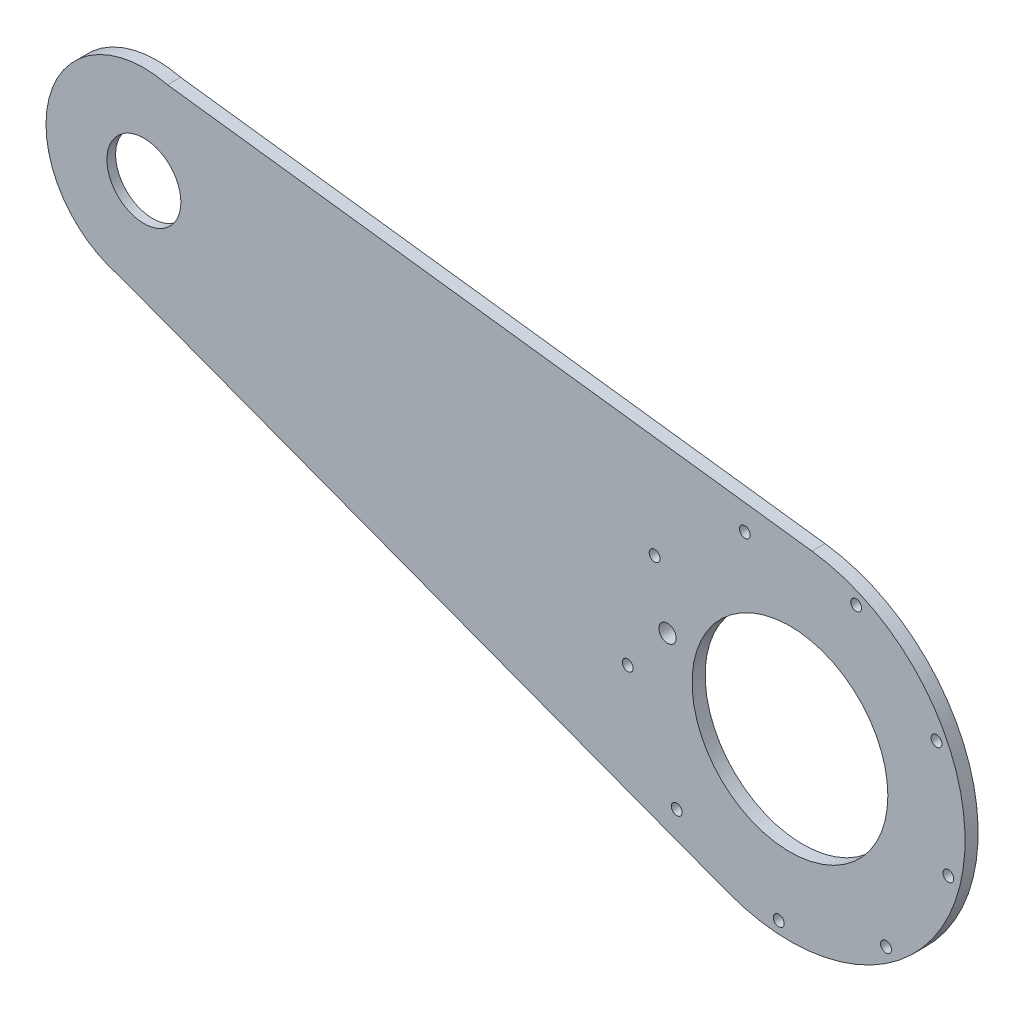
SolidWorks part; units mm, degrees
ref_plane "前视基准面" through (0, 0, 0) normal (0, 0, 1) x (1, 0, 0)
ref_plane "上视基准面" through (0, 0, 0) normal (0, 1, 0) x (1, 0, 0)
ref_plane "右视基准面" through (0, 0, 0) normal (1, 0, 0) x (0, 0, -1)
sketch "草图2" plane through (0, 0, 0) normal (0, 0, 1) x (1, 0, 0)
  line L0 (-94.4003, 60.3379) -> (-122.5464, 67.3235)
  line L1 (-122.5464, 67.3235) -> (-342.1674, 121.8314) construction
  line L2 (-242.8951, 97.1929) -> (-234.6136, 130.5606) construction
  line L3 (-242.8951, 97.1929) -> (-252.9342, 56.7435) construction
  line L4 (-248.3149, 75.3555) -> (-108.6007, 22.6761)
  line L5 (-237.4752, 119.0304) -> (-89.3429, 100.2689)
  arc A6 (-120.6052, 66.8418) -> (-124.4875, 67.8053) centre (-122.5464, 67.3235) ccw
  arc A7 (-124.4875, 67.8053) -> (-120.6052, 66.8418) centre (-122.5464, 67.3235) ccw
  arc A8 (-122.6148, 83.0399) -> (-121.1101, 83.7225) centre (-122.6148, 85.0399) ccw
  arc A9 (-123.8343, 83.4547) -> (-122.6148, 83.0399) centre (-122.6148, 85.0399) ccw
  arc A10 (-123.8343, 83.4547) -> (-125.5111, 84.0251) centre (-125.5111, 81.2751) ccw
  arc A11 (-125.5111, 84.0251) -> (-126.8989, 78.901) centre (-125.5111, 81.2751) ccw
  arc A12 (-126.1212, 76.2764) -> (-126.8989, 78.901) centre (-127.9083, 77.1743) ccw
  arc A13 (-126.1212, 76.2764) -> (-126.7049, 75.0573) centre (-94.4003, 60.3379) ccw
  arc A14 (-129.1382, 73.9829) -> (-126.7049, 75.0573) centre (-128.5249, 75.8865) ccw
  arc A15 (-129.1382, 73.9829) -> (-131.6495, 72.7096) centre (-129.7514, 72.0792) ccw
  arc A16 (-131.6495, 72.7096) -> (-133.1115, 66.8189) centre (-94.4003, 60.3379) ccw
  arc A17 (-133.1115, 66.8189) -> (-131.487, 64.5192) centre (-131.139, 66.4887) ccw
  arc A18 (-129.8385, 62.4317) -> (-131.487, 64.5192) centre (-131.835, 62.5497) ccw
  arc A19 (-129.8385, 62.4317) -> (-129.8925, 61.0828) centre (-94.4003, 60.3379) ccw
  arc A20 (-130.6064, 59.5927) -> (-129.8925, 61.0828) centre (-131.892, 61.1248) ccw
  arc A21 (-131.8073, 59.1266) -> (-130.6064, 59.5927) centre (-131.892, 61.1248) ccw
  arc A22 (-131.8073, 59.1266) -> (-133.4584, 58.4857) centre (-131.6907, 56.3791) ccw
  arc A23 (-133.4584, 58.4857) -> (-131.2278, 53.6683) centre (-131.6907, 56.3791) ccw
  arc A24 (-128.9449, 52.1577) -> (-131.2278, 53.6683) centre (-130.8911, 51.6968) ccw
  arc A25 (-128.9449, 52.1577) -> (-122.0677, 38.0946) centre (-94.4003, 60.3379) ccw
  arc A26 (-121.6568, 36.4942) -> (-122.0677, 38.0946) centre (-123.6264, 36.8415) ccw
  arc A27 (-122.2771, 35.3652) -> (-121.6568, 36.4942) centre (-123.6264, 36.8415) ccw
  arc A28 (-122.2771, 35.3652) -> (-123.1299, 33.813) centre (-120.4217, 33.3354) ccw
  arc A29 (-123.1299, 33.813) -> (-118.3246, 31.5564) centre (-120.4217, 33.3354) ccw
  arc A30 (-115.6049, 31.8666) -> (-118.3246, 31.5564) centre (-116.7995, 30.2626) ccw
  arc A31 (-115.6049, 31.8666) -> (-101.297, 25.5143) centre (-94.4003, 60.3379) ccw
  arc A32 (-99.9535, 24.5524) -> (-101.297, 25.5143) centre (-101.6856, 23.5524) ccw
  arc A33 (-99.703, 23.2889) -> (-99.9535, 24.5524) centre (-101.6856, 23.5524) ccw
  arc A34 (-99.703, 23.2889) -> (-99.3585, 21.5516) centre (-96.977, 22.9266) ccw
  arc A35 (-99.3585, 21.5516) -> (-94.227, 22.9117) centre (-96.977, 22.9266) ccw
  arc A36 (-92.3429, 24.8976) -> (-94.227, 22.9117) centre (-92.227, 22.901) ccw
  arc A37 (-92.3429, 24.8976) -> (-77.2993, 29.2283) centre (-94.4003, 60.3379) ccw
  arc A38 (-75.6518, 29.3551) -> (-77.2993, 29.2283) centre (-76.3358, 27.4757) ccw
  arc A39 (-74.6477, 28.5482) -> (-75.6518, 29.3551) centre (-76.3358, 27.4757) ccw
  arc A40 (-74.6477, 28.5482) -> (-73.2671, 27.4387) centre (-72.3266, 30.0229) ccw
  arc A41 (-73.2671, 27.4387) -> (-70.2105, 31.7792) centre (-72.3266, 30.0229) ccw
  arc A42 (-70.0437, 34.5115) -> (-70.2105, 31.7792) centre (-68.6715, 33.0565) ccw
  arc A43 (-70.0437, 34.5115) -> (-61.3033, 47.4989) centre (-94.4003, 60.3379) ccw
  arc A44 (-60.1227, 48.655) -> (-61.3033, 47.4989) centre (-59.4387, 46.7756) ccw
  arc A45 (-58.8349, 48.6823) -> (-60.1227, 48.655) centre (-59.4387, 46.7756) ccw
  arc A46 (-58.8349, 48.6823) -> (-57.0642, 48.7198) centre (-58.0047, 51.304) ccw
  arc A47 (-57.0642, 48.7198) -> (-57.5126, 54.0096) centre (-58.0047, 51.304) ccw
  arc A48 (-59.1411, 56.2099) -> (-57.5126, 54.0096) centre (-57.1547, 55.9773) ccw
  arc A49 (-59.1411, 56.2099) -> (-58.9003, 60.3379) centre (-94.4003, 60.3379) ccw
  arc A50 (-58.9003, 60.3379) -> (-60.7938, 71.777) centre (-94.4003, 60.3379) ccw
  arc A51 (-60.6325, 73.4215) -> (-60.7938, 71.777) centre (-58.9004, 72.4215) ccw
  arc A52 (-59.6635, 74.2702) -> (-60.6325, 73.4215) centre (-58.9004, 72.4215) ccw
  arc A53 (-59.6635, 74.2702) -> (-58.3312, 75.4371) centre (-60.7127, 76.8121) ccw
  arc A54 (-58.3312, 75.4371) -> (-62.0749, 79.2011) centre (-60.7127, 76.8121) ccw
  arc A55 (-64.7367, 79.8398) -> (-62.0749, 79.2011) centre (-63.0655, 80.9385) ccw
  arc A56 (-64.7367, 79.8398) -> (-76.0091, 90.7026) centre (-94.4003, 60.3379) ccw
  arc A57 (-76.9426, 92.066) -> (-76.0091, 90.7026) centre (-74.973, 92.4133) ccw
  arc A58 (-76.7458, 93.339) -> (-76.9426, 92.066) centre (-74.973, 92.4133) ccw
  arc A59 (-76.7458, 93.339) -> (-76.4753, 95.0894) centre (-79.1835, 94.6118) ccw
  arc A60 (-76.4753, 95.0894) -> (-81.7626, 95.5663) centre (-79.1835, 94.6118) ccw
  arc A61 (-84.2122, 94.3446) -> (-81.7626, 95.5663) centre (-83.6383, 96.2605) ccw
  arc A62 (-84.2122, 94.3446) -> (-99.8299, 95.4203) centre (-94.4003, 60.3379) ccw
  arc A63 (-101.4213, 95.8646) -> (-99.8299, 95.4203) centre (-100.1357, 97.3967) ccw
  arc A64 (-102.0889, 96.9663) -> (-101.4213, 95.8646) centre (-100.1357, 97.3967) ccw
  arc A65 (-102.0889, 96.9663) -> (-103.0068, 98.481) centre (-104.7744, 96.3744) ccw
  arc A66 (-103.0068, 98.481) -> (-107.3636, 95.4478) centre (-104.7744, 96.3744) ccw
  arc A67 (-108.4548, 92.9373) -> (-107.3636, 95.4478) centre (-109.2467, 94.7739) ccw
  arc A68 (-108.4548, 92.9373) -> (-121.1101, 83.7225) centre (-94.4003, 60.3379) ccw
  circle A69 centre (-360.001, 29.9468) radius 11.5
  circle A70 centre (-360.001, 29.9468) radius 22.5
  circle A71 centre (-360.001, 29.9468) radius 8.5
  circle A72 centre (-242.8951, 97.1929) radius 8.5
  circle A73 centre (-242.8951, 97.1929) radius 11.5
  circle A74 centre (-242.8951, 97.1929) radius 22.5
  circle A75 centre (-94.4003, 60.3379) radius 40.25
  circle A76 centre (-94.4003, 60.3379) radius 22.5
  point P0 (-242.8951, 97.1929)
  point P27 (-237.4752, 119.0304)
  point P137 (-360.001, 41.4468)
  point P139 (-360.001, 18.4468)
  point P140 (-248.3149, 75.3555)
  dimension "D2" = 17
  dimension "D3" = 23
  dimension "D4" = 45
  dimension "D1" = 17
  dimension "D6" = 153
  dimension "D7" = 45
  dimension "D5" = 23
  dimension "D8" = 45
extrude "凸台-拉伸1" add sketch "草图2" along normal blind 3 contours A75 L5 A74 L4 | A74 A73 | A54 A75 A60 A59 A58 A57 A56 A55 | A60 A75 A66 A65 A64 A63 A62 A61 | A66 A75 A11 A10 A9 A8 A68 A67 | A11 A75 A23 A22 A21 A20 A19 A18 A17 A16 A15 A14 A13 A12 | A23 A75 A29 A28 A27 A26 A25 A24 | A29 A75 A35 A34 A33 A32 A31 A30 | A35 A75 A41 A40 A39 A38 A37 A36 | A41 A75 A47 A46 A45 A44 A43 A42 | A47 A75 A54 A53 A52 A51 A50 A49 A48 | A67 A68 A8 A9 A10 A11 A12 A13 A14 A15 A16 A17 A18 A19 A20 A21 A22 A23 A24 A25 A26 A27 A28 A29 A30 A31 A32 A33 A34 A35 A36 A37 A38 A39 A40 A41 A42 A43 A44 A45 A46 A47 A48 A49 A50 region at (-172.9122, 79.8238, 0) region at (-264.1149, 102.4595, 0) region at (-109.6196, 26.0582, 0) region at (-128.0936, 43.8609, 0) region at (-121.9734, 32.8304, 0) region at (-84.0244, 24.2953, 0) region at (-91.8231, 97.7557, 0) region at (-133.192, 69.9667, 0) region at (-63.2841, 39.3972, 0) region at (-68.3744, 87.345, 0) region at (-116.4777, 90.6581, 0) region at (-57.1035, 64.2975, 0)
extrude "凸台-拉伸2" add sketch "草图2<3>" along normal blind 2 from offset 1 contours A73 A72 region at (-254.0698, 97.1929, 0)
sketch "草图2<3>" plane through (0, 0, 0) normal (0, 0, 1) x (1, 0, 0) same geometry as "草图2"
hole_wizard "M3 螺纹孔1" positions "草图3" profile "草图4" tap size "M3" standard "GB" end condition through all
sketch "草图3" plane through (0, 0, 3) normal (0, 0, 1) x (1, 0, 0)
  point P0 (-79.1835, 94.6118)
  point P3 (-60.7127, 76.8121)
  point P6 (-58.0047, 51.304)
  point P9 (-72.3266, 30.0229)
  point P12 (-96.977, 22.9266)
  point P15 (-120.4217, 33.3354)
  point P18 (-131.6907, 56.3791)
  point P21 (-125.5111, 81.2751)
  point P24 (-104.7744, 96.3744)
sketch "草图4" plane through (-79.1835, 94.6118, 3) normal (1, 0, 0) x (0, -1, 0)
  line L0 (0, 0) -> (0, 3)
  line L1 (0, 3) -> (1.25, 3)
  line L2 (1.25, 3) -> (1.25, 0)
  line L5 (1.25, 0) -> (0, 0)
  line L11 (0, -6.35) -> (0, 107.95) construction
  dimension "通孔螺纹孔钻头直径" = 2.5
  dimension "通孔螺纹孔钻头深度" = 3
cosmetic thread "孔螺蚊线1" parameters "D2"=3
cosmetic thread "孔螺蚊线2" parameters "D2"=3
cosmetic thread "孔螺蚊线3" parameters "D2"=3
cosmetic thread "孔螺蚊线4" parameters "D2"=3
cosmetic thread "孔螺蚊线5" parameters "D2"=3
cosmetic thread "孔螺蚊线6" parameters "D2"=3
cosmetic thread "孔螺蚊线7" parameters "D2"=3
cosmetic thread "孔螺蚊线8" parameters "D2"=3
cosmetic thread "孔螺蚊线9" parameters "D2"=3
sketch "草图5" plane through (0, 0, 3) normal (0, 0, 1) x (1, 0, 0)
  line L0 (-263.6523, 128.1032) -> (-32.3931, 70.7068) construction
  line L1 (-265.9204, 77.1491) -> (-86.0659, 32.511) construction
  line L2 (-182.604, 112.0808) -> (-183.1066, 108.1125)
  line L3 (-237.4752, 119.0304) -> (-89.3429, 100.2689) construction
  circle A0 centre (-242.8951, 97.1929) radius 8.5 construction
  circle A1 centre (-242.8951, 97.1929) radius 8.5
  circle A2 centre (-242.8951, 97.1929) radius 25 construction
  circle A3 centre (-94.4003, 60.3379) radius 22.5 construction
  circle A4 centre (-94.4003, 60.3379) radius 22.5
  circle A5 centre (-94.4003, 60.3379) radius 25 construction
  dimension "D1" = 50
  dimension "D2" = 50
  dimension "D3" = 4
